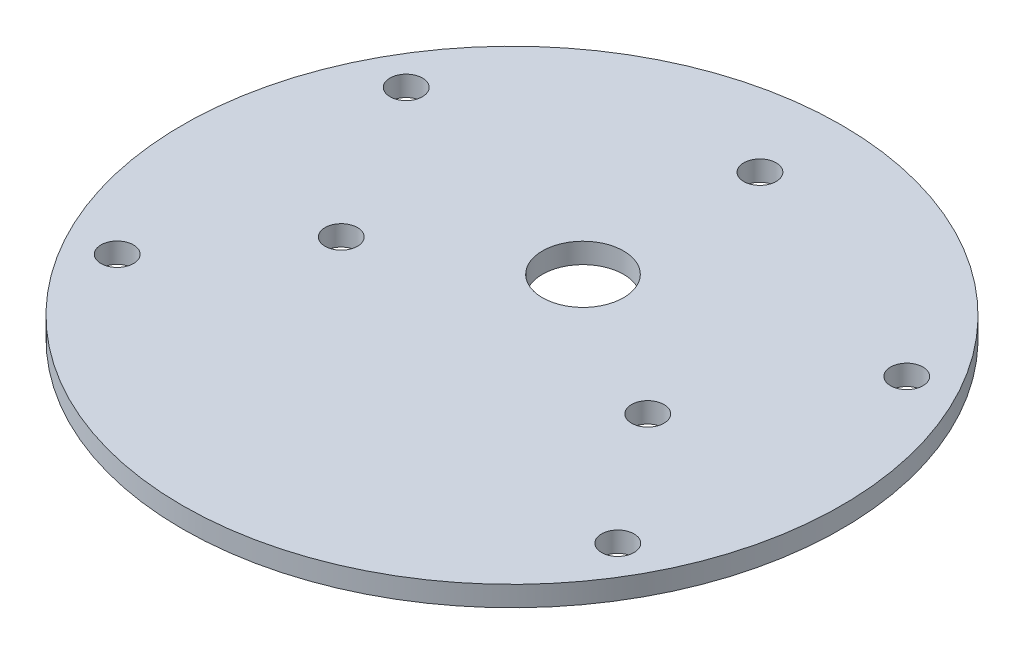
SolidWorks part; units mm, degrees
ref_plane "前视基准面" through (0, 0, 0) normal (0, 0, 1) x (1, 0, 0)
ref_plane "上视基准面" through (0, 0, 0) normal (0, 1, 0) x (1, 0, 0)
ref_plane "右视基准面" through (0, 0, 0) normal (1, 0, 0) x (0, 0, -1)
sketch "草图1" plane through (0, 0, 0) normal (0, 1, 0) x (1, 0, 0)
  line L0 (0, 0) -> (28.1458, -16.25) construction
  line L1 (0, 0) -> (32.5, 0) construction
  line L2 (0, 0) -> (0, -32.5) construction
  circle A0 centre (0, 0) radius 32.5
  circle A2 centre (24.6817, 14.25) radius 1.6
  circle A3 centre (0, 7) radius 4
  circle A11 centre (-24.6817, 14.25) radius 1.6
  circle A12 centre (24.6817, -14.25) radius 1.6
  circle A16 centre (0, 24.45) radius 1.6
  circle A17 centre (15.1121, -1.725) radius 1.6
  circle A18 centre (-15.1121, -1.725) radius 1.6
  circle A20 centre (-24.6817, -14.25) radius 1.6
  point P5 (0, 24.45)
  point P21 (0, 7)
  dimension "D1" = 3.2
  dimension "D2" = 65
  dimension "D6" = 3.2
  dimension "D5" = 30
  dimension "D7" = 4
  dimension "D4" = 3
extrude "凸台-拉伸1" add sketch "草图1" along normal blind 2
